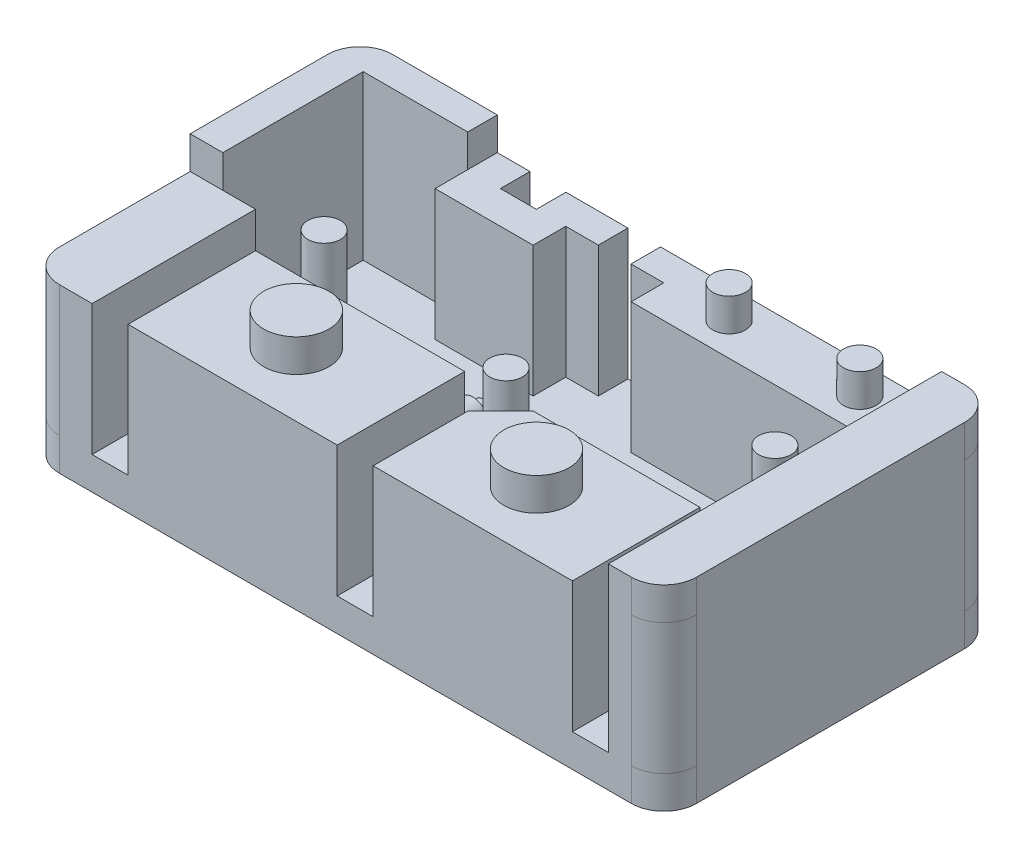
SolidWorks part; units mm, degrees
material "PP Kopolimer"
ref_plane "Front Plane" through (0, 0, 0) normal (0, 0, 1) x (1, 0, 0)
ref_plane "Top Plane" through (0, 0, 0) normal (0, 1, 0) x (1, 0, 0)
ref_plane "Right Plane" through (0, 0, 0) normal (1, 0, 0) x (0, 0, -1)
sketch "Szkic1" plane through (0, 0, 0) normal (0, 1, 0) x (1, 0, 0)
  line L1 (9.75, -5.1) -> (-9.75, -5.1)
  line L2 (9.75, -5.1) -> (9.75, 5.1)
  line L3 (9.75, 5.1) -> (-9.75, 5.1)
  line L4 (-9.75, -5.1) -> (-9.75, 5.1)
  line L5 (9.75, -5.1) -> (-9.75, 5.1) construction
  line L6 (9.75, 5.1) -> (-9.75, -5.1) construction
  point P0 (0, 0)
  dimension "D1" = 10.2
  dimension "D2" = 19.5
extrude "Dodanie-wyciągnięcie2" add sketch "Szkic1" along normal blind 1 contours L3 L4 L1 L2
fillet "Zaokrąglenie1" radius 1 1 edges at (-9.75, 0.5, 5.1)
fillet "Zaokrąglenie2" radius 1 1 edges at (-9.75, 0.5, -5.1)
fillet "Zaokrąglenie3" radius 1 1 edges at (9.75, 0.5, 5.1)
fillet "Zaokrąglenie4" radius 1 1 edges at (9.75, 0.5, -5.1)
sketch "Szkic4" plane through (0, 1, 0) normal (0, 1, 0) x (1, 0, 0)
  line L0 (-9.75, -4.1) -> (-9.75, 4.1) construction
  line L1 (-8.75, -0.1) -> (-7.75, -0.1)
  line L3 (-9.75, -5.1) -> (-7.75, -5.1)
  line L4 (-7.75, -0.1) -> (-7.75, -5.1)
  line L5 (8.75, -5.1) -> (-8.75, -5.1) construction
  line L6 (-7.75, -4.1915) -> (-6.65, -4.1915) construction
  line L7 (-6.65, -4.1915) -> (-0.25, -4.1915) construction
  line L8 (-0.25, -4.1915) -> (0.85, -4.1915) construction
  line L9 (0.85, -4.1915) -> (6.95, -4.1915) construction
  line L10 (6.95, -4.1915) -> (8.05, -4.1915) construction
  line L11 (9.75, -4.1) -> (9.75, 4.1) construction
  line L12 (-6.65, -5.1) -> (-0.25, -5.1)
  line L13 (-6.65, -5.1) -> (-6.65, -1.2)
  line L14 (-6.65, -1.2) -> (-0.25, -1.2)
  line L15 (-0.25, -5.1) -> (-0.25, -1.2)
  line L16 (0.85, -5.1) -> (6.95, -5.1)
  line L17 (0.85, -5.1) -> (0.85, -2.2)
  line L18 (1.85, -1.2) -> (6.95, -1.2)
  line L19 (6.95, -5.1) -> (6.95, -1.2)
  line L20 (8.05, -5.1) -> (9.75, -5.1)
  line L21 (8.05, -5.1) -> (8.05, 3.1953)
  line L23 (9.75, -5.1) -> (9.75, 5.1)
  line L24 (8.75, 5.1) -> (-8.75, 5.1) construction
  line L25 (-9.75, 5.1) -> (-4.55, 5.1)
  line L27 (-8.75, -0.1) -> (-8.75, 4.1953)
  line L30 (-0.5538, 5.1) -> (9.75, 5.1)
  line L31 (-8.75, 4.1953) -> (-5.55, 4.1953)
  line L34 (-4.55, 4.1953) -> (-4.55, 5.1)
  line L35 (-9.75, 5.1) -> (-9.75, -5.1)
  line L36 (-4.55, 4.1953) -> (-3.45, 4.1953)
  line L37 (-5.55, 4.1953) -> (-5.55, 3.1953)
  line L38 (-5.55, 3.1953) -> (-2.55, 3.1953)
  line L39 (-2.55, 4.1953) -> (-2.55, 3.1953)
  line L40 (-2.55, 4.1953) -> (-1.5525, 4.1953)
  line L41 (-3.45, 4.1953) -> (-3.45, 5.1)
  line L42 (-3.45, 5.1) -> (-1.5525, 5.1)
  line L43 (-1.5525, 4.1953) -> (-1.5525, 5.1)
  line L44 (0.85, -2.2) -> (1.85, -1.2)
  line L45 (0.85, -5.1) -> (0.85, -2.2) construction
  line L46 (-0.5538, 4.1953) -> (0.45, 4.1953)
  line L47 (-0.5538, 4.1953) -> (-0.5538, 5.1)
  line L51 (0.45, 4.1953) -> (0.45, 3.1953)
  line L52 (0.45, 3.1953) -> (8.05, 3.1953)
  circle A1 centre (0.2797, -0.4607) radius 0.5
  circle A3 centre (-6.15, 0.4) radius 0.5
  circle A4 centre (6.45, 1.5953) radius 0.5
  dimension "D33" = 1
  dimension "D34" = 1
  dimension "D35" = 1
  dimension "D2" = 5
  dimension "D4" = 0
  dimension "D5" = 6.4
  dimension "D6" = 0
  dimension "D7" = 3.9
  dimension "D8" = 0
  dimension "D9" = 2
  dimension "D10" = 1
  dimension "D11" = 4.2
  dimension "D12" = 3
  dimension "D13" = 1
  dimension "D14" = 4.2953
  dimension "D15" = 1.9047
  dimension "D16" = 1.8975
  dimension "D17" = 0.9047
  dimension "D18" = 0.9047
  dimension "D19" = 1.1
  dimension "D20" = 7.6
  dimension "D23" = 3.2
  dimension "D25" = 8.2953
  dimension "D26" = 5.1
  dimension "D29" = 3.9
  dimension "D31" = 1.0038
  dimension "D32" = 0.9047
extrude "Dodanie-wyciągnięcie4" add sketch "Szkic4" along normal blind 4
fillet "Zaokrąglenie5" radius 1 1 edges at (-9.75, 3, 5.1)
fillet "Zaokrąglenie6" radius 1 1 edges at (-9.75, 3, -5.1)
fillet "Zaokrąglenie7" radius 1 1 edges at (9.75, 3, -5.1)
fillet "Zaokrąglenie8" radius 1 1 edges at (9.75, 3, 5.1)
sketch "Szkic8" plane through (0, 5, 0) normal (0, 1, 0) x (1, 0, 0)
  line L0 (-3.45, -5.1) -> (-3.45, -1.2) construction
  line L1 (-6.65, -5.1) -> (-0.25, -5.1) construction
  line L2 (-0.25, -1.2) -> (-6.65, -1.2) construction
  line L3 (-0.25, -3.15) -> (-6.65, -3.15) construction
  line L4 (-0.25, -5.1) -> (-0.25, -1.2) construction
  line L5 (-6.65, -1.2) -> (-6.65, -5.1) construction
  line L6 (3.9, -5.1) -> (3.9, -1.2) construction
  line L7 (0.85, -5.1) -> (6.95, -5.1) construction
  line L8 (6.95, -1.2) -> (1.85, -1.2) construction
  line L9 (6.95, -3.15) -> (0.85, -3.15) construction
  line L10 (6.95, -5.1) -> (6.95, -1.2) construction
  line L11 (0.85, -2.2) -> (0.85, -5.1) construction
  line L12 (0.45, 4.1953) -> (2.45, 4.1953) construction
  line L13 (2.45, 4.1953) -> (4.45, 4.1953) construction
  line L14 (4.45, 4.1953) -> (6.45, 4.1953) construction
  line L15 (9.75, -4.1) -> (9.75, 4.1) construction
  line L16 (-8.75, -0.1) -> (-9.75, -0.1)
  line L17 (-8.75, -0.1) -> (-8.75, 4.1953)
  line L19 (-9.75, -0.1) -> (-9.75, 5.1)
  line L20 (-9.75, 5.1) -> (-5.55, 5.1)
  line L21 (-5.55, 4.1953) -> (-8.75, 4.1953)
  line L22 (-5.55, 4.1953) -> (-5.55, 5.1)
  line L23 (9.75, -5.1) -> (8.05, -5.1)
  line L24 (9.75, -5.1) -> (9.75, 5.1)
  line L25 (9.75, 5.1) -> (8.05, 5.1)
  line L26 (8.05, -5.1) -> (8.05, 5.1)
  line L27 (8.75, 5.1) -> (-0.5538, 5.1) construction
  line L28 (8.05, -5.1) -> (8.75, -5.1) construction
  circle A0 centre (-3.45, -3.15) radius 1
  circle A1 centre (3.9, -3.15) radius 1
  circle A2 centre (6.45, 4.1953) radius 0.5
  circle A3 centre (2.45, 4.1953) radius 0.5
  dimension "D1" = 1.7
  dimension "D2" = 1
  dimension "D3" = 0
  dimension "D4" = 0
extrude "Dodanie-wyciągnięcie12" add sketch "Szkic8" along normal blind 1
fillet "Zaokrąglenie12" radius 1 3 edges at (9.75, 5.5, -5.1) (9.75, 5.5, 5.1) (-9.75, 5.5, -5.1)
sketch "Szkic12" plane through (0, 0, 1.2) normal (0, 0, -1) x (-1, 0, 0)
  circle A0 centre (1, 3) radius 0.25
extrude "Dodanie-wyciągnięcie14" add sketch "Szkic12" along normal blind 1.3
sketch "Szkic15" plane through (0, 0, 1.2) normal (0, 0, -1) x (-1, 0, 0)
  circle A0 centre (1, 3) radius 0.3981
  circle A1 centre (1, 3) radius 0.4504
extrude "Dodanie-wyciągnięcie15" add sketch "Szkic15" along normal blind 1
